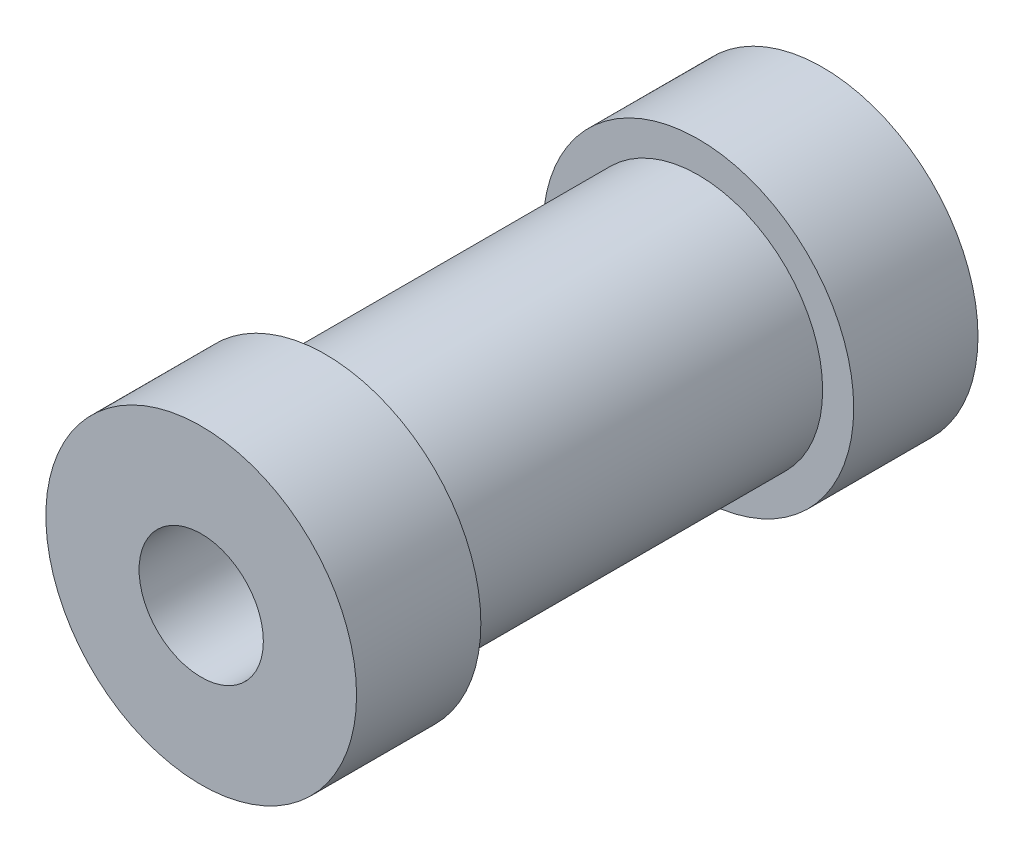
SolidWorks part; units mm, degrees
material "PE High Density"
ref_plane "Front Plane" through (0, 0, 0) normal (0, 0, 1) x (1, 0, 0)
ref_plane "Top Plane" through (0, 0, 0) normal (0, 1, 0) x (1, 0, 0)
ref_plane "Right Plane" through (0, 0, 0) normal (1, 0, 0) x (0, 0, -1)
sketch "Sketch1" plane through (0, 0, 0) normal (0, 0, 1) x (1, 0, 0)
  circle A0 centre (0, 0) radius 0.5
  circle A1 centre (0, 0) radius 1.25
  circle A2 centre (0, 0) radius 1
  dimension "D1" = 1
  dimension "D2" = 2.5
  dimension "D3" = 2
extrude "Boss-Extrude1" add sketch "Sketch1" along normal mid plane 3 contours A2
sketch "Sketch2" plane through (0, 0, 1.5) normal (0, 0, 1) x (1, 0, 0)
  circle A0 centre (0, 0) radius 1.25
  dimension "D1" = 2.5
extrude "Boss-Extrude2" add sketch "Sketch2" along normal blind 1
mirror "Mirror1" about plane through (0, 0, 0) normal (0, 0, 1) of "Boss-Extrude2"
extrude "Cut-Extrude1" cut sketch "Sketch1<4>" against normal through all both and the other way through all contours A0
sketch "Sketch1<4>" plane through (0, 0, 0) normal (0, 0, 1) x (1, 0, 0) same geometry as "Sketch1"
